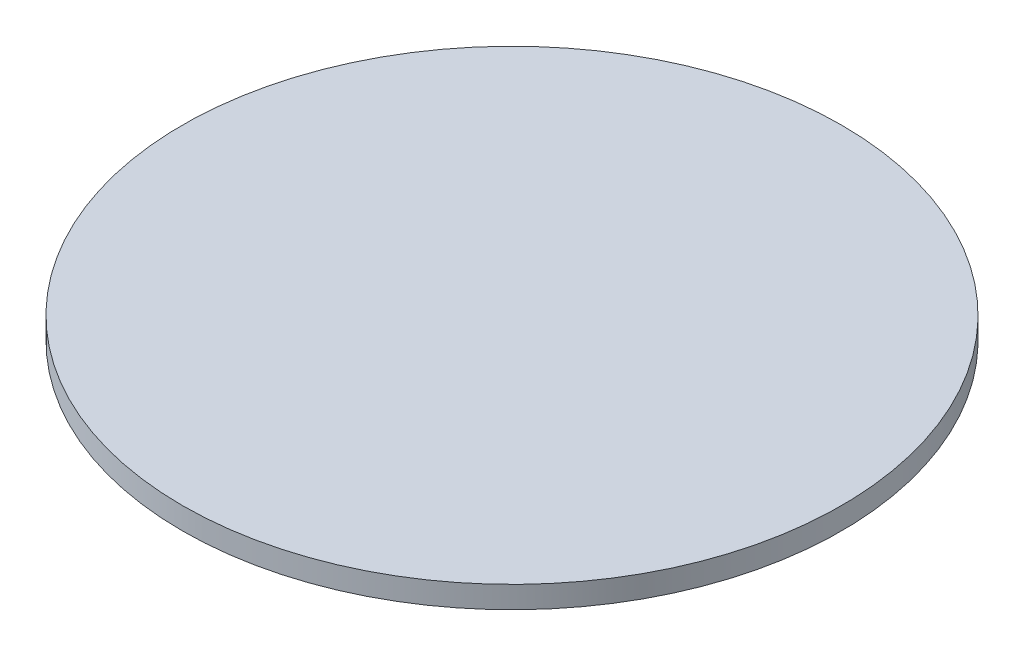
SolidWorks part; units mm, degrees
ref_plane "Ebene vorne" through (0, 0, 0) normal (0, 0, 1) x (1, 0, 0)
ref_plane "Ebene oben" through (0, 0, 0) normal (0, 1, 0) x (1, 0, 0)
ref_plane "Ebene rechts" through (0, 0, 0) normal (1, 0, 0) x (0, 0, -1)
sketch "Skizze1" plane through (0, 0, 0) normal (0, 1, 0) x (1, 0, 0)
  circle A0 centre (0, 0) radius 10
  dimension "D1" = 20
extrude "Aufsatz-Linear austragen1" add sketch "Skizze1" against normal blind 2
sketch "Skizze2" plane through (0, 0, 0) normal (0, 1, 0) x (1, 0, 0)
  circle A0 centre (0, 0) radius 30
  dimension "D1" = 60
extrude "Aufsatz-Linear austragen2" add sketch "Skizze2" along normal blind 2
sketch "Skizze3" plane through (0, -2, 0) normal (0, -1, 0) x (1, 0, 0)
  line L0 (-7.0711, 7.0711) -> (-9.1924, 9.1924)
  line L1 (7.0711, 7.0711) -> (9.1924, 9.1924)
  line L2 (7.0711, -7.0711) -> (9.1924, -9.1924)
  line L3 (-7.0711, -7.0711) -> (-9.1924, -9.1924)
  arc A0 (9.1924, 9.1924) -> (9.1924, -9.1924) centre (0, 0) cw
  arc A1 (-9.1924, 9.1924) -> (-9.1924, -9.1924) centre (0, 0) ccw
  circle A2 centre (0, 0) radius 10 construction
  circle A3 centre (0, 0) radius 10 construction
  arc A4 (-7.0711, 7.0711) -> (-7.0711, -7.0711) centre (0, 0) ccw
  arc A5 (7.0711, 7.0711) -> (7.0711, -7.0711) centre (0, 0) cw
extrude "Aufsatz-Linear austragen3" add sketch "Skizze3" along normal blind 2 separate body
sketch "Skizze4" plane through (0, -2, 0) normal (0, -1, 0) x (1, 0, 0)
  circle A0 centre (0, 0) radius 10
extrude "Aufsatz-Linear austragen4" add sketch "Skizze4" along normal blind 2
sketch "Skizze8" plane through (0, -2, 0) normal (0, 1, 0) x (1, 0, 0)
  line L0 (9.1924, -9.1924) -> (7.0711, -7.0711) construction
  line L1 (10.0765, -8.2136) -> (7.7376, -6.3348)
  line L2 (9.1924, -9.1924) -> (7.0711, -7.0711)
  line L3 (-7.0711, 7.0711) -> (-9.1924, 9.1924)
  line L4 (-10.0575, 8.2369) -> (-7.7328, 6.3407)
  arc A0 (7.0711, -7.0711) -> (7.7376, -6.3348) centre (0, 0) ccw
  arc A1 (9.1924, -9.1924) -> (10.0765, -8.2136) centre (0, 0) ccw
  arc A2 (-7.0711, 7.0711) -> (-7.7328, 6.3407) centre (0, 0) ccw
  arc A3 (-9.1924, 9.1924) -> (-10.0575, 8.2369) centre (0, 0) ccw
extrude "Aufsatz-Linear austragen15" add sketch "Skizze8" along normal blind 3
